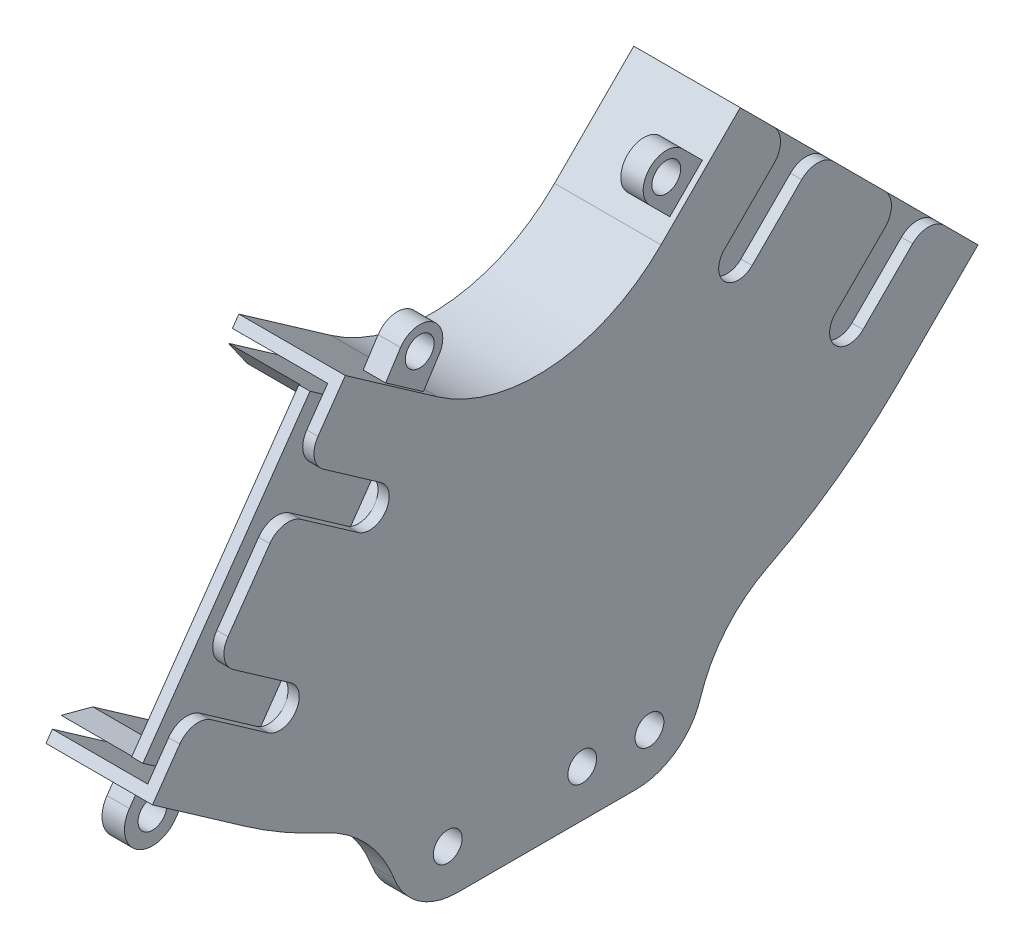
SolidWorks part; units mm, degrees
ref_plane "Front Plane" through (0, 0, 0) normal (0, 0, 1) x (1, 0, 0)
ref_plane "Top Plane" through (0, 0, 0) normal (0, 1, 0) x (1, 0, 0)
ref_plane "Right Plane" through (0, 0, 0) normal (1, 0, 0) x (0, 0, -1)
sketch "Sketch3" plane through (0, 0, 0) normal (1, 0, 0) x (0, 0, -1)
  line L0 (-22.7274, -32.4581) -> (-62.0633, -88.6355)
  line L1 (28.0184, -28.0184) -> (76.5118, -76.5118)
  line L2 (-22.7274, -32.4581) -> (0, 0) construction
  line L3 (0, 0) -> (28.0184, -28.0184) construction
  line L4 (0, 40.513) -> (0, -40.513) construction
  line L5 (-62.0633, -88.6355) -> (-66.4339, -94.8775)
  line L6 (76.5118, -76.5118) -> (81.8999, -81.8999)
  arc A2 (-62.0633, -88.6355) -> (76.5118, -76.5118) centre (0, 0) ccw
  arc A4 (-27.098, -38.7) -> (33.4066, -33.4066) centre (0, 0) ccw
  arc A5 (-22.7274, -32.4581) -> (28.0184, -28.0184) centre (0, 0) ccw
  arc A6 (-66.4339, -94.8775) -> (81.8999, -81.8999) centre (0, 0) ccw
  dimension "D1" = 216.408
  dimension "D2" = 135
  dimension "D3" = 94.488
  dimension "D4" = 7.62
  dimension "D6" = 7.62
  dimension "D5" = 80
extrude "Base extrude" add sketch "Sketch3" along normal blind 58.42 contours L5 A6 L6 A2 | A5 L0 A4 L1 region at (0, -39.9408, -3.4944) region at (0, -109.321, -9.5643)
sketch "Sketch4" plane through (58.42, 0, 0) normal (1, 0, 0) x (0, 0, -1)
  line L0 (-66.4339, -94.8775) -> (-22.7274, -32.4581)
  line L1 (28.0184, -28.0184) -> (81.8999, -81.8999)
  arc A0 (-22.7274, -32.4581) -> (28.0184, -28.0184) centre (0, 0) ccw
  arc A1 (-22.7274, -32.4581) -> (28.0184, -28.0184) centre (0, 0) ccw construction
  arc A2 (-66.4339, -94.8775) -> (81.8999, -81.8999) centre (0, 0) ccw
  arc A3 (-66.4339, -94.8775) -> (81.8999, -81.8999) centre (0, 0) ccw construction
  arc M1 (28.0184, -28.0184) -> (-22.7274, -32.4581) centre (0, 0) cw
  line M2 (-22.7274, -32.4581) -> (-27.098, -38.7)
  arc M3 (-27.098, -38.7) -> (33.4066, -33.4066) centre (0, 0) ccw
  line M4 (33.4066, -33.4066) -> (28.0184, -28.0184)
extrude "Outer wall" add sketch "Sketch4" along normal blind 7.62 contours L0 A2 L1 M3 | M4 M1 M2 M3 region at (58.42, -79.1939, -6.9286) region at (58.42, -39.9408, -3.4944)
ref_plane "Midplane" through (29.21, 0, 0) normal (-1, 0, 0) x (0, 0, 1)
mirror "Mirror1" about plane through (29.21, 0, 0) normal (-1, 0, 0) of "Outer wall"
sketch "Sketch6" plane through (0, 0, 0) normal (0, 0.5736, 0.8192) x (1, 0, 0)
  line L27 (-5.08, -42.164) -> (63.5, -42.164)
  line L28 (-5.08, -42.164) -> (-5.08, -113.284)
  line L29 (-5.08, -113.284) -> (63.5, -113.284)
  line L30 (63.5, -42.164) -> (63.5, -113.284)
  line L31 (-2.54, -44.704) -> (60.96, -44.704)
  line L32 (-2.54, -44.704) -> (-2.54, -110.744)
  line L33 (-2.54, -110.744) -> (60.96, -110.744)
  line L34 (60.96, -44.704) -> (60.96, -110.744)
  line L35 (58.42, -47.244) -> (0, -47.244) construction
  line L36 (0, -108.204) -> (0, -18.7894) construction
  line L37 (58.42, -18.7894) -> (58.42, -108.204) construction
  line L38 (58.42, -108.204) -> (0, -108.204) construction
  line L40 (0, -47.244) -> (58.42, -47.244)
  line L41 (0, -47.244) -> (0, -108.204)
  line L42 (0, -108.204) -> (58.42, -108.204)
  line L43 (58.42, -47.244) -> (58.42, -108.204)
  line L44 (-7.62, -39.624) -> (66.04, -39.624)
  line L45 (-7.62, -39.624) -> (-7.62, -115.824)
  line L46 (-7.62, -115.824) -> (66.04, -115.824)
  line L47 (66.04, -39.624) -> (66.04, -115.824)
  line M21 (-7.62, -39.624) -> (-7.62, -115.824)
  line M22 (-7.62, -115.824) -> (66.04, -115.824)
  line M23 (66.04, -115.824) -> (66.04, -39.624)
  line M24 (66.04, -39.624) -> (-7.62, -39.624)
  line M25 (58.42, -108.204) -> (0, -108.204)
  line M26 (0, -108.204) -> (0, -47.244)
  line M27 (0, -47.244) -> (58.42, -47.244)
  line M28 (58.42, -47.244) -> (58.42, -108.204)
  dimension "D1" = 2.54
  dimension "D2" = 2.54
  dimension "D3" = 2.54
  dimension "D4" = 2.54
  dimension "D5" = 2.54
  dimension "D6" = 2.54
  dimension "D7" = 2.54
  dimension "D8" = 2.54
extrude "Endcap 1" add sketch "Sketch6" along normal blind 25.4 contours L27 L30 L29 L28 M24 M21 M22 M23 | L34 L31 L32 L33 M28 M25 M26 M27 region at (29.21, -37.3698, 26.1667) region at (29.21, -33.3262, 23.3353)
sketch "Sketch7" plane through (0, 0, 0) normal (0, 0.7071, -0.7071) x (1, 0, 0)
  line L0 (-5.08, 113.284) -> (63.5, 113.284)
  line L1 (-5.08, 113.284) -> (-5.08, 42.164)
  line L2 (-5.08, 42.164) -> (63.5, 42.164)
  line L3 (63.5, 113.284) -> (63.5, 42.164)
  line L4 (-2.54, 110.744) -> (60.96, 110.744)
  line L5 (-2.54, 110.744) -> (-2.54, 44.704)
  line L6 (-2.54, 44.704) -> (60.96, 44.704)
  line L7 (60.96, 110.744) -> (60.96, 44.704)
  line L8 (0, 108.204) -> (58.42, 108.204)
  line L9 (0, 108.204) -> (0, 47.244)
  line L10 (0, 47.244) -> (58.42, 47.244)
  line L11 (58.42, 108.204) -> (58.42, 47.244)
  line L12 (-7.62, 115.824) -> (66.04, 115.824)
  line L13 (-7.62, 115.824) -> (-7.62, 39.624)
  line L14 (-7.62, 39.624) -> (66.04, 39.624)
  line L15 (66.04, 115.824) -> (66.04, 39.624)
  line L16 (58.42, 108.204) -> (0, 108.204) construction
  line L17 (58.42, 47.244) -> (58.42, 108.204) construction
  line L18 (66.04, 115.824) -> (-7.62, 115.824) construction
  line L19 (66.04, 39.624) -> (66.04, 115.824) construction
  line L20 (-7.62, 39.624) -> (-7.62, 115.824) construction
  line L21 (66.04, 39.624) -> (-7.62, 39.624) construction
  line M17 (66.04, 115.824) -> (-7.62, 115.824)
  line M18 (-7.62, 115.824) -> (-7.62, 39.624)
  line M19 (-7.62, 39.624) -> (66.04, 39.624)
  line M20 (66.04, 39.624) -> (66.04, 115.824)
  line M21 (0, 47.244) -> (0, 108.204)
  line M22 (0, 108.204) -> (58.42, 108.204)
  line M23 (58.42, 108.204) -> (58.42, 47.244)
  line M24 (58.42, 47.244) -> (0, 47.244)
  dimension "D1" = 2.54
  dimension "D2" = 2.54
  dimension "D3" = 2.54
  dimension "D4" = 2.54
  dimension "D5" = 2.54
  dimension "D6" = 2.54
  dimension "D7" = 2.54
  dimension "D8" = 2.54
extrude "Endcap 2" add sketch "Sketch7" along normal blind 25.4 contours L0 L3 L2 L1 M20 M17 M18 M19 | L7 L4 L5 L6 M24 M21 M22 M23 region at (29.21, -77.66, -77.66) region at (29.21, -81.1505, -81.1505)
chamfer "Internal Chamfer" distance 7.62 angle 20 4 edges at (29.21, -74.0667, 82.8697) (29.21, -24.1312, 47.9045) (29.21, -58.5513, -94.4723) (29.21, -15.446, -51.3671) first distance on face at (29.21, -81.3511, 72.4665) first distance on face at (29.21, -31.4156, 37.5013) first distance on face at (29.21, -67.5315, -85.492) first distance on face at (29.21, -24.4263, -42.3868)
ref_plane "Plane2" through (0, -13.9736, -1.2225) normal (0, -0.9962, -0.0872) x (-1, 0, 0)
sketch "Sketch10" plane through (0, -13.9736, -1.2225) normal (0, -0.9962, -0.0872) x (-1, 0, 0)
  line L0 (-66.04, 93.9078) -> (7.62, 93.9078) construction
  line L1 (-16.51, 95.5358) -> (-41.91, 95.5358)
  line L2 (-16.51, 95.5358) -> (-16.51, -82.1857)
  line L3 (-16.51, -82.1857) -> (-41.91, -82.1857)
  line L4 (-41.91, 95.5358) -> (-41.91, -82.1857)
  point P4 (-29.21, 93.9078)
  point P5 (-29.21, 95.5358)
  dimension "D1" = 25.4
extrude "Flywheel Hole" cut sketch "Sketch10" along normal up to next
sketch "Sketch11" plane through (-7.62, 0, 0) normal (-1, 0, 0) x (0, 0, 1)
  line L0 (-25.2982, 2.2719) -> (-28.0184, -28.0184)
  line L4 (-3.0636, -22.3183) -> (-4.5937, -39.3568)
  line L5 (6.8995, -21.445) -> (11.3704, -37.9575)
  line L6 (-20.4217, -1.79) -> (20.4217, 1.79) construction
  line L7 (24.5172, 6.6383) -> (33.1306, -25.1737)
  line L8 (43.5339, -17.8892) -> (22.7274, -32.4581) construction
  line L10 (1.5525, -17.7121) -> (-2.2178, 25.303) construction
  line L11 (22.7274, -32.4581) -> (43.5339, -17.8892)
  line L12 (22.7274, -32.4581) -> (33.1306, -25.1737)
  arc A1 (-28.0184, -28.0184) -> (22.7274, -32.4581) centre (0, 0) ccw construction
  circle A3 centre (0, 0) radius 4.064
  arc A4 (24.5172, 6.6383) -> (-25.2982, 2.2719) centre (0, 0) ccw
  circle A6 centre (-20.4217, -1.79) radius 2.5
  circle A7 centre (20.4217, 1.79) radius 2.5
  arc A8 (-3.0636, -22.3183) -> (6.8995, -21.445) centre (1.9961, -22.7727) cw
  arc A11 (11.3704, -37.9575) -> (22.7274, -32.4581) centre (0, 0) ccw
  arc A12 (-28.0184, -28.0184) -> (22.7274, -32.4581) centre (0, 0) ccw
  arc A13 (-28.0184, -28.0184) -> (-4.5937, -39.3568) centre (0, 0) ccw
  point P22 (0, 0)
  dimension "D3" = 8.128
  dimension "D2" = 25.4
  dimension "D1" = 5
  dimension "D5" = 5.08
  dimension "D4" = 41
  dimension "D7" = 43.18
  dimension "D6" = 0
extrude "Flywheel holder" add sketch "Sketch11" against normal blind 7.62
sketch "Sketch12" plane through (-7.62, 0, 0) normal (-1, 0, 0) x (0, 0, 1)
  circle A0 centre (0, 0) radius 14.605
  dimension "D1" = 29.21
extrude "Motor insert" cut sketch "Sketch12" against normal blind 6.35
sketch "Sketch14" plane through (-7.62, 0, 0) normal (-1, 0, 0) x (0, 0, 1)
  line L1 (-106.5763, 40.9543) -> (105.556, 40.9543)
  line L2 (-106.5763, 40.9543) -> (-106.5763, -120.0185)
  line L3 (-106.5763, -120.0185) -> (105.556, -120.0185)
  line L4 (105.556, 40.9543) -> (105.556, -120.0185)
extrude "Cut-Extrude2" cut sketch "Sketch14" against normal up to surface (49.53 mm away) up to face at (41.91, -26.9401, -2.3569)
sketch "Sketch15" plane through (41.91, 0, 0) normal (-1, 0, 0) x (0, 0, 1)
  line L0 (-93.8083, -77.7308) -> (-89.6212, -74.1787)
  line L1 (-99.8604, -63.9394) -> (-81.8999, -81.8999) construction
  line L2 (-89.6212, -74.1787) -> (-80.6312, -83.1493)
  line L3 (-80.6312, -83.1493) -> (-85.0539, -86.9012)
  line L4 (-16.51, -121.4959) -> (-16.51, -114.6413)
  line L5 (-16.51, -114.6413) -> (-3.8593, -115.7597)
  line L6 (-3.8593, -115.7597) -> (-3.8593, -120.7059)
  line L7 (63.1155, -104.8839) -> (59.3284, -99.4753)
  line L8 (59.3284, -99.4753) -> (69.9059, -92.4464)
  line L9 (66.4339, -94.8775) -> (87.2404, -80.3086) construction
  line L10 (69.9059, -92.4464) -> (73.4123, -97.454)
  circle A0 centre (-89.7004, -82.5731) radius 3.2639
  circle A1 centre (-10.16, -121.4959) radius 3.2639
  circle A2 centre (68.1904, -101.0671) radius 3.2639
  arc A3 (-93.8083, -77.7308) -> (-85.0539, -86.9012) centre (-89.7004, -82.5731) ccw
  arc A5 (62.868, -104.5305) -> (73.3715, -97.3959) centre (68.1904, -101.0671) ccw
  arc A6 (-81.8999, -81.8999) -> (66.4339, -94.8775) centre (0, 0) ccw construction
  arc A7 (-16.51, -121.4959) -> (-3.8593, -120.7059) centre (-10.16, -121.4959) ccw
  line M28 (-99.8604, -63.9394) -> (-81.8999, -81.8999)
  arc M29 (-81.8999, -81.8999) -> (66.4339, -94.8775) centre (0, 0) ccw
  line M30 (66.4339, -94.8775) -> (87.2404, -80.3086)
  dimension "D4" = 6.5278
  dimension "D5" = 12.7
  dimension "D1" = 121.92
  dimension "D2" = 121.92
  dimension "D3" = 121.92
  dimension "D6" = 10.16
  dimension "D7" = 10.16
  dimension "D8" = 19.05
  dimension "D9" = 12.7
  dimension "D10" = 12.7
  dimension "D11" = 12.7
extrude "Joining screw holes" add sketch "Sketch15" against normal blind 5.08 contours L0 A3 L3 A0 M29 M28 | L4 A7 L6 A1 M29 | L7 A5 L10 A2 M30 M29 region at (41.91, -97.4205, 63.0391) region at (41.91, -115.5565, -10.2161) region at (41.91, -76.1174, -91.5767)
ref_plane "Plane3" through (59.69, 0, 0) normal (1, 0, 0) x (0, 0, -1)
sketch "Sketch16" plane through (59.69, 0, 0) normal (1, 0, 0) x (0, 0, -1)
  line L0 (-43.5339, -17.8892) -> (-22.7274, -32.4581) construction
  line L1 (45.9789, -10.0579) -> (28.0184, -28.0184) construction
  line L2 (-29.7459, -19.9251) -> (-33.1306, -25.1737)
  line L3 (-33.1306, -25.1737) -> (-24.5641, -31.172)
  line L4 (-24.5641, -31.172) -> (-21.1794, -25.9235)
  line L5 (26.7818, -20.2747) -> (31.2719, -24.7649)
  line L6 (31.2719, -24.7649) -> (38.6683, -17.3685)
  line L7 (38.6683, -17.3685) -> (34.1782, -12.8783)
  line L8 (34.1782, -12.8783) -> (26.7818, -20.2747) construction
  circle A0 centre (-25.4, -22.8348) radius 3.2639
  circle A1 centre (30.48, -16.5765) radius 3.2639
  arc A2 (-21.1794, -25.9235) -> (-29.8435, -20.0764) centre (-25.4, -22.8348) ccw
  arc A3 (34.1782, -12.8783) -> (26.7818, -20.2747) centre (30.48, -16.5765) ccw
  dimension "D3" = 6.5278
  dimension "D1" = 6.35
  dimension "D2" = 6.35
  dimension "D4" = 25.4
  dimension "D5" = 30.48
  dimension "D6" = 55.88
  dimension "D7" = 6.2582
extrude "Flywheel cover connectors" add sketch "Sketch16" along normal blind 5.08 contours L4 A2 L2 L3 A0 | L7 L8 A1 L5 L6 | L8 A3 A1 region at (59.69, -18.7043, 22.5078) region at (59.69, -19.2478, -33.1513) region at (59.69, -12.9676, -26.8711)
sketch "Sketch17" plane through (66.04, 0, 0) normal (1, 0, 0) x (0, 0, -1)
  line L0 (-30.48, -111.7415) -> (-30.48, -132.08)
  line L1 (-30.48, -132.08) -> (35.56, -132.08)
  line L2 (35.56, -132.08) -> (35.56, -110.2301)
  circle A0 centre (-20.32, -121.92) radius 3.2639
  circle A1 centre (25.4, -121.92) radius 3.2639
  arc A2 (-66.4339, -94.8775) -> (81.8999, -81.8999) centre (0, 0) ccw construction
  circle A4 centre (10.16, -121.4959) radius 3.2639
  arc A5 (-66.4339, -94.8775) -> (81.8999, -81.8999) centre (0, 0) ccw
  arc A6 (-30.48, -111.7415) -> (35.56, -110.2301) centre (0, 0) ccw
  circle A7 centre (10.16, -121.4959) radius 3.2639 construction
  dimension "D1" = 6.5278
  dimension "D2" = 20.32
  dimension "D3" = 25.4
  dimension "D4" = 121.92
  dimension "D5" = 0
  dimension "D6" = 10.16
  dimension "D7" = 10.16
  dimension "D8" = 10.16
extrude "80-20 connector" add sketch "Sketch17" against normal blind 5.08
fillet "Fillet1" radius 30.48 2 edges at (63.5, -111.7415, 30.48) (63.5, -110.2301, -35.56)
fillet "Fillet2" radius 15.24 2 edges at (63.5, -132.08, -35.56) (63.5, -132.08, 30.48)
sketch "Sketch18" plane through (66.04, 0, 0) normal (1, 0, 0) x (0, 0, -1)
  line L0 (-35.474, -42.9126) -> (-52.6394, -30.8933)
  line L1 (-87.2404, -80.3086) -> (-43.5339, -17.8892) construction
  line L2 (-52.6394, -30.8933) -> (-57.7385, -38.1755)
  line L3 (-57.7385, -38.1755) -> (-40.5731, -50.1948)
  line L4 (-55.8704, -72.0416) -> (-73.0358, -60.0223)
  line L5 (-73.0358, -60.0223) -> (-78.1349, -67.3046)
  line L6 (-78.1349, -67.3046) -> (-60.9695, -79.3239)
  line L7 (42.3868, -36.1006) -> (57.2042, -21.2832)
  line L8 (45.9789, -10.0579) -> (99.8604, -63.9394) construction
  line L9 (57.2042, -21.2832) -> (63.4904, -27.5694)
  line L10 (63.4904, -27.5694) -> (48.673, -42.3868)
  line L11 (67.5315, -61.2453) -> (82.3489, -46.4279)
  line L12 (82.3489, -46.4279) -> (88.6351, -52.7141)
  line L13 (88.6351, -52.7141) -> (73.8177, -67.5315)
  line L14 (-43.5339, -17.8892) -> (-22.7274, -32.4581) construction
  line L15 (45.9789, -10.0579) -> (28.0184, -28.0184) construction
  line L16 (99.8604, -63.9394) -> (81.8999, -81.8999) construction
  line L17 (-87.2404, -80.3086) -> (-66.4339, -94.8775) construction
  line L18 (-24.1843, -34.5387) -> (-64.977, -92.7968) construction
  arc A0 (-40.5731, -50.1948) -> (-35.474, -42.9126) centre (-38.0236, -46.5537) ccw
  arc A1 (-60.9695, -79.3239) -> (-55.8704, -72.0416) centre (-58.42, -75.6827) ccw
  arc A2 (42.3868, -36.1006) -> (48.673, -42.3868) centre (45.5299, -39.2437) ccw
  arc A3 (67.5315, -61.2453) -> (73.8177, -67.5315) centre (70.6746, -64.3884) ccw
  dimension "D1" = 8.89
  dimension "D3" = 20.32
  dimension "D4" = 20.32
  dimension "D5" = 20.32
  dimension "D6" = 20.32
extrude "Support Removal" cut sketch "Sketch18" against normal up to next
fillet "Fillet3" radius 5.08 8 edges at (64.77, -52.7141, -88.6351) (64.77, -46.4279, -82.3489) (64.77, -27.5694, -63.4904) (64.77, -21.2832, -57.2042) (64.77, -67.3046, 78.1349) (64.77, -60.0223, 73.0358) (64.77, -38.1755, 57.7385) (64.77, -30.8933, 52.6394)
